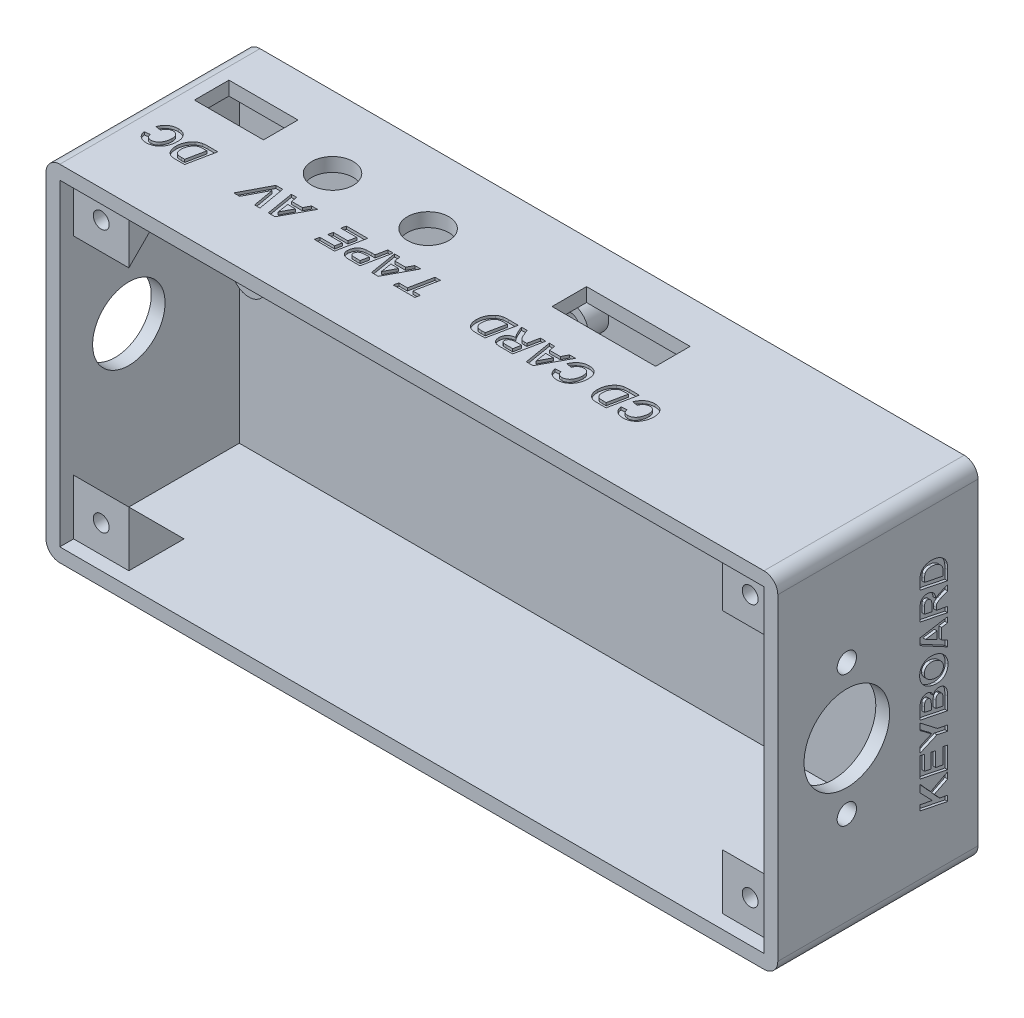
SolidWorks part; units mm, degrees
material "ABS"
ref_plane "Спереди" through (0, 0, 0) normal (0, 0, 1) x (1, 0, 0)
ref_plane "Сверху" through (0, 0, 0) normal (0, 1, 0) x (1, 0, 0)
ref_plane "Справа" through (0, 0, 0) normal (1, 0, 0) x (0, 0, -1)
sketch "Эскиз1" plane through (0, 0, 0) normal (0, 0, 1) x (1, 0, 0)
  line L1 (-53, -25) -> (53, -25)
  line L2 (-53, -25) -> (-53, 25)
  line L3 (-53, 25) -> (53, 25)
  line L4 (53, -25) -> (53, 25)
  line L5 (-53, -25) -> (53, 25) construction
  line L6 (-53, 25) -> (53, -25) construction
  point P0 (0, 0)
  dimension "D1" = 106
  dimension "D2" = 50
extrude "CaseBody" add sketch "Эскиз1" along normal blind 3
sketch "Эскиз2" plane through (0, 0, 3) normal (0, 0, 1) x (1, 0, 0)
  line L0 (53, 25) -> (-53, 25) construction
  line L1 (-51, -23) -> (51, -23)
  line L2 (-51, -23) -> (-51, 23)
  line L3 (-51, 23) -> (51, 23)
  line L4 (51, -23) -> (51, 23)
  line L5 (-51, -23) -> (51, 23) construction
  line L6 (-51, 23) -> (51, -23) construction
  line L7 (53, -25) -> (53, 25) construction
  line L9 (-53, -25) -> (53, -25)
  line L10 (-53, -25) -> (-53, 25)
  line L11 (-53, 25) -> (53, 25)
  line L12 (53, -25) -> (53, 25)
  line L13 (-53, -25) -> (53, 25) construction
  line L14 (-53, 25) -> (53, -25) construction
  point P0 (0, 0)
  point P10 (0, 0)
  dimension "D1" = 2
  dimension "D2" = 2
extrude "CaseBody2" add sketch "Эскиз2" along normal blind 26
sketch "Эскиз3" plane through (0, 0, 3) normal (0, 0, 1) x (1, 0, 0)
  line L0 (51, 23) -> (-51, 23) construction
  line L1 (-46.625, 1.53) -> (46.625, 1.53) construction
  line L2 (-46.625, 1.53) -> (-46.625, 19.18) construction
  line L3 (-46.625, 19.18) -> (46.625, 19.18) construction
  line L4 (46.625, 1.53) -> (46.625, 19.18) construction
  line L5 (-46.625, 1.53) -> (46.625, 19.18) construction
  line L6 (-46.625, 19.18) -> (46.625, 1.53) construction
  circle A0 centre (-46.625, 1.53) radius 2.5
  circle A1 centre (46.625, 1.53) radius 2.5
  circle A2 centre (0.005, 19.18) radius 2.5
  point P0 (0, 0)
  point P13 (0, 10.355)
  dimension "D4" = 5
  dimension "D1" = 93.25
  dimension "D2" = 17.65
  dimension "D3" = 46.63
  dimension "D5" = 3.82
extrude "SizifXXSFix" add sketch "Эскиз3" along normal blind 3
sketch "Эскиз4" plane through (0, 0, 6) normal (0, 0, 1) x (1, 0, 0)
  circle A0 centre (-46.625, 1.53) radius 1.2
  circle A1 centre (0.005, 19.18) radius 1.2
  circle A2 centre (46.625, 1.53) radius 1.2
  dimension "D1" = 2.4
extrude "Holes2_5" cut sketch "Эскиз4" against normal blind 5.6
sketch "Эскиз5" plane through (0, 25, 0) normal (0, 1, 0) x (1, 0, 0)
  line L1 (-49.3, -6.2) -> (-39.3, -6.2)
  line L2 (-49.3, -6.2) -> (-49.3, -11.2)
  line L3 (-49.3, -11.2) -> (-39.3, -11.2)
  line L4 (-39.3, -6.2) -> (-39.3, -11.2)
  line L5 (-49.3, -6.2) -> (-39.3, -11.2) construction
  line L6 (-49.3, -11.2) -> (-39.3, -6.2) construction
  line L7 (2.5, -6.2) -> (17.5, -6.2)
  line L8 (2.5, -6.2) -> (2.5, -11.2)
  line L9 (2.5, -11.2) -> (17.5, -11.2)
  line L10 (17.5, -6.2) -> (17.5, -11.2)
  line L11 (2.5, -6.2) -> (17.5, -11.2) construction
  line L12 (2.5, -11.2) -> (17.5, -6.2) construction
  line L13 (53, 0) -> (-53, 0) construction
  line L14 (-53, -29) -> (-53, 0) construction
  circle A0 centre (-30.1, -10.4) radius 3
  circle A1 centre (-16.25, -10.4) radius 3
  point P0 (-44.3, -8.7)
  point P9 (10, -8.7)
  dimension "D5" = 6
  dimension "D2" = 10
  dimension "D3" = 6.2
  dimension "D4" = 5
  dimension "D6" = 13.85
  dimension "D7" = 14.2
  dimension "D8" = 26.25
  dimension "D9" = 10.4
  dimension "D10" = 5
  dimension "D11" = 15
  dimension "D12" = 22.9
extrude "SizifXXS_Holes" cut sketch "Эскиз5" against normal up to next
sketch "Эскиз7" plane through (53, 0, 0) normal (1, 0, 0) x (0, 0, -1)
  line L0 (-20, 0) -> (-6.0564, 0) construction
  line L2 (0, -25) -> (0, 25) construction
  circle A0 centre (-19, 0) radius 6.2
  circle A1 centre (-19, -9.5) radius 1.4
  circle A2 centre (-19, 9.5) radius 1.4
  dimension "D1" = 12.4
  dimension "D4" = 2.8
  dimension "D2" = 19
  dimension "D3" = 19
extrude "PS2Hole" cut sketch "Эскиз7" against normal up to next
sketch "Эскиз8" plane through (51, 0, 0) normal (-1, 0, 0) x (0, 0, 1)
  line L0 (27, 23) -> (27, 15)
  line L1 (29, 23) -> (3, 23) construction
  line L2 (27, 15) -> (19, 23)
  line L3 (19, 23) -> (27, 23)
  line L4 (29, -23) -> (29, 23) construction
  dimension "D1" = 8
  dimension "D2" = 8
  dimension "D3" = 2
extrude "CaseTopFix" add sketch "Эскиз8" along normal blind 8
sketch "Эскиз9" plane through (0, 0, 27) normal (0, 0, 1) x (1, 0, 0)
  line L0 (43, 15) -> (43, 23) construction
  line L1 (43, 23) -> (51, 23) construction
  line L2 (43, 23) -> (43, 15) construction
  line L3 (43, 15) -> (51, 15) construction
  line L4 (51, 23) -> (51, 15) construction
  line L5 (43, 23) -> (51, 15) construction
  line L6 (43, 15) -> (51, 23) construction
  line L7 (43, 23) -> (51, 23) construction
  circle A0 centre (47, 19) radius 1.15
  point P0 (47, 19)
  dimension "D1" = 2.3
extrude "CaseTopHoles" cut sketch "Эскиз9" against normal up to next
mirror "CaseTopHoles1" about plane through (0, 0, 0) normal (0, 1, 0) of "CaseTopHoles", "CaseTopFix"
mirror "CaseTopHoles2" about plane through (0, 0, 0) normal (1, 0, 0) of "CaseTopHoles", "CaseTopHoles1", "CaseTopFix"
fillet "Fillet" radius 2 4 edges at (-53, 25, 14.5) (53, 25, 14.5) (53, -25, 14.5) (-53, -25, 14.5)
sketch "Эскиз10" plane through (0, 25, 0) normal (0, 1, 0) x (1, 0, 0)
  line L0 (51, 0) -> (-51, 0) construction
  line L1 (-53, -29) -> (-53, 0) construction
  text T0 "<r180>VA</r>" font "Times New Roman" height 4
  text T1 "<r180>EPAT</r>" font "Times New Roman" height 4
  text T2 "<r180>CD</r>" font "Times New Roman" height 4
  text T3 "<r180>DRAC DC</r>" font "Times New Roman" height 4
  dimension "D1" = 16
  dimension "D2" = 22.5962
  dimension "D3" = 11.2585
  dimension "D4" = 14.4528
  dimension "D5" = 21.8
extrude "InterfaceInfo" cut sketch "Эскиз10" against normal blind 0.4
sketch "Эскиз11" plane through (53, 0, 0) normal (1, 0, 0) x (0, 0, -1)
  line L0 (-4.4, -15.5) -> (-4.4, 15.5) construction
  line L1 (0, -23) -> (0, 23) construction
  text T0 "KEYBOARD" font "Arial" height 4
  point P0 (-4.4, 0)
  dimension "D1" = 4.4
  dimension "D2" = 31
extrude "PS2Info" cut sketch "Эскиз11" against normal blind 0.4
sketch "Эскиз12" plane through (0, 23, 0) normal (0, -1, 0) x (1, 0, 0)
  line L1 (-53, 0) -> (-53, 29) construction
  line L2 (-51, 0) -> (51, 0) construction
  text T0 "© Peter Ukhov 2023" font "Arial" height 6
  dimension "D1" = 16
  dimension "D2" = 14
sketch "Эскиз13" plane through (-53, 0, 0) normal (-1, 0, 0) x (0, 0, 1)
  line L1 (0, 23) -> (0, -23) construction
  circle A0 centre (19, 0) radius 5.25
  dimension "D1" = 10.5
  dimension "D2" = 19
extrude "ButtonHole" cut sketch "Эскиз13" against normal up to next
sketch "Эскиз14" plane through (-53, 0, 0) normal (-1, 0, 0) x (0, 0, 1)
  line L0 (6.2274, 10.1387) -> (6.2274, -12.1287) construction
  text T0 "POWER" font "Arial" height 4
extrude "ButtonInfo" cut sketch "Эскиз14" against normal blind 0.4
extrude "CopyLeft" cut sketch "Эскиз12" against normal blind 0.4
equation "\"D1@Эскиз1\"=100+2*2+2"
equation "\"D5@Эскиз3\"=3.42+0.4"
